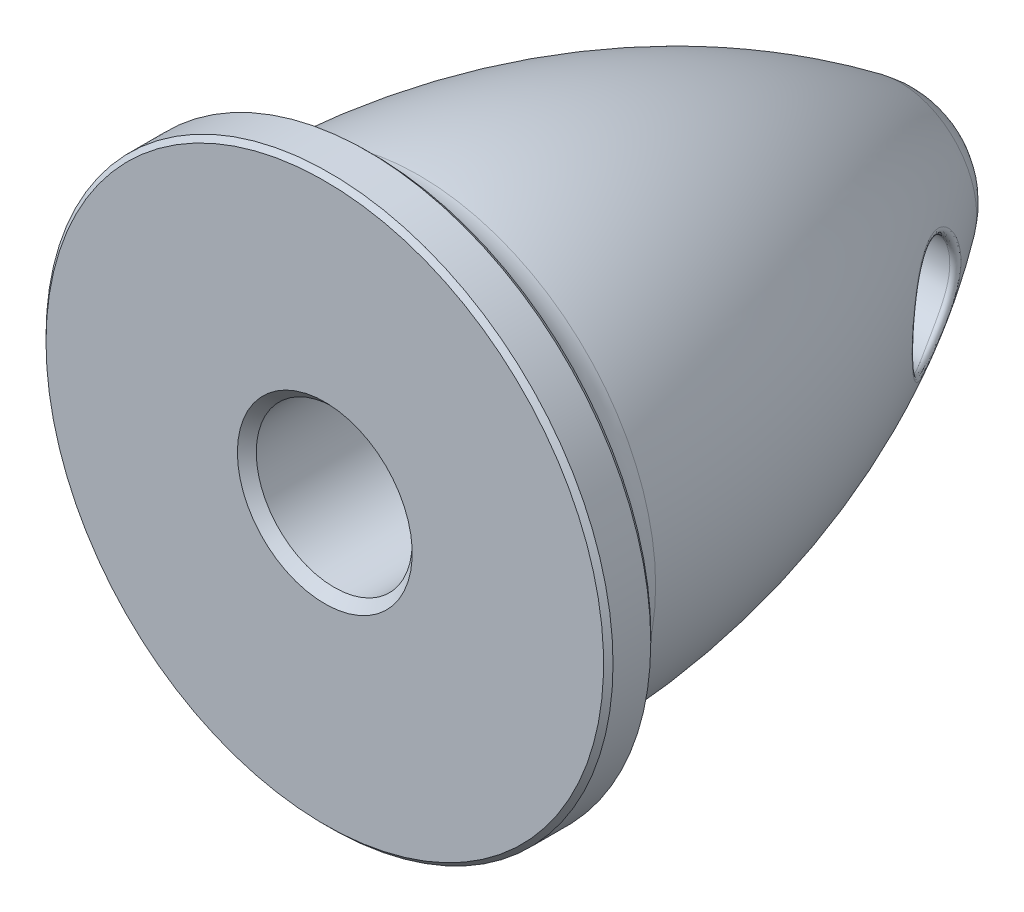
SolidWorks part; units mm, degrees
ref_plane "Plan de face" through (0, 0, 0) normal (0, 0, 1) x (1, 0, 0)
ref_plane "Plan de dessus" through (0, 0, 0) normal (0, 1, 0) x (1, 0, 0)
ref_plane "Plan de droite" through (0, 0, 0) normal (1, 0, 0) x (0, 0, -1)
sketch "Esquisse1" plane through (0, 0, 0) normal (1, 0, 0) x (0, 0, -1)
  line L0 (0, 0) -> (0, 6)
  line L1 (0, 6) -> (1, 6)
  line L2 (1, 6) -> (1, 5)
  line L3 (0, 0) -> (11, 0)
  line L4 (-1000, 0) -> (49000, 0) construction
  line L5 (11, 0) -> (13, 0)
  arc A0 (1, 5) -> (12.1794, 1.6152) centre (1.7547, -12.6619) cw
  arc A1 (13, 0) -> (12.1794, 1.6152) centre (11, 0) ccw
  dimension "D4" = 4
  dimension "D5" = 1
  dimension "D1" = 1
  dimension "D2" = 12
  dimension "D3" = 11
revolve "Révolution1" add sketch "Esquisse1" angle 360 about L4
fillet "Congé1" radius 1 1 edges at (5, 0, -1)
chamfer "Chanfrein1" distance 0.1 angle 45 2 edges at (6, 0, 0) (6, 0, -1) first distance on face at (6, 0, 0) first distance on face at (5.0146, 0, -1.9868)
sketch "Esquisse2" plane through (0, 0, 0) normal (1, 0, 0) x (0, 0, -1)
  circle A0 centre (10, 0) radius 1
  dimension "D1" = 2
  dimension "D2" = 10
extrude "Enlèv. mat.-Extru.1" cut sketch "Esquisse2" against normal through all and the other way through all
fillet "Congé2" radius 0.1 2 edges at (-3.1857, 0.7917, -9.3891) (3.2619, 0.6932, -9.2792)
hole_wizard "Trou pour taraudage pour trou taraudé M41" positions "Esquisse4" profile "Esquisse3" hole size "M4" standard "Iso"
sketch "Esquisse4" plane through (0, 0, 0) normal (0, 0, 1) x (1, 0, 0)
  point P0 (0, 0)
sketch "Esquisse3" plane through (0, 0, 0) normal (1, 0, 0) x (0, -1, 0)
  line L0 (0, 0) -> (0, 7.9914)
  line L1 (0, 7.9914) -> (1.65, 7)
  line L2 (1.65, 7) -> (1.65, 0)
  line L5 (1.65, 0) -> (0, 0)
  line L10 (0, 7.9914) -> (-1.65, 7) construction
  line L11 (0, -6.35) -> (0, 107.95) construction
  dimension "Diamètre du perçage" = 3.3
  dimension "Profondeur du perçage" = 7
  dimension "Angle de pointe" = 118
chamfer "Chanfrein2" distance 0.2 angle 45 1 edges at (1.65, 0, 0)
